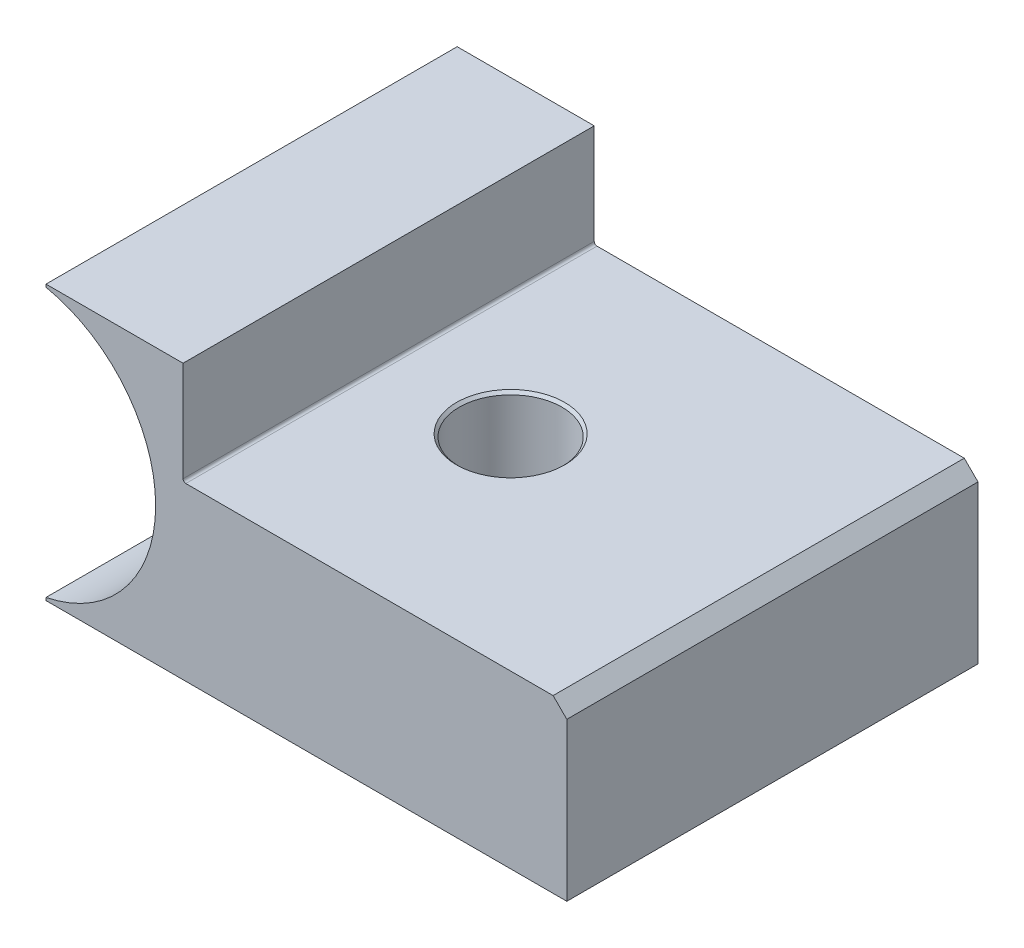
SolidWorks part; units mm, degrees
material "AISI Type A2 Tool Steel Custom"
ref_plane "Front Plane" through (0, 0, 0) normal (0, 0, 1) x (1, 0, 0)
ref_plane "Top Plane" through (0, 0, 0) normal (0, 1, 0) x (1, 0, 0)
ref_plane "Right Plane" through (0, 0, 0) normal (1, 0, 0) x (0, 0, -1)
sketch "Sketch1" plane through (0, 0, 0) normal (0, 0, 1) x (1, 0, 0)
  line L1 (2.54, 0) -> (50.8, 0)
  line L3 (2.54, 25.4) -> (15.24, 25.4)
  line L4 (50.8, 0) -> (50.8, 15.875)
  line L5 (2.54, 25.4) -> (2.54, 25.1434)
  line L6 (15.24, 25.4) -> (15.24, 15.875)
  line L7 (15.24, 15.875) -> (50.8, 15.875)
  line L8 (2.54, 0.2566) -> (2.54, 0)
  arc A1 (2.54, 0.2566) -> (2.54, 25.1434) centre (0, 12.7) ccw
  dimension "D2" = 25.4
  dimension "D1" = 12.7
  dimension "D3" = 9.525
  dimension "D4" = 2.54
  dimension "D5" = 35.56
  dimension "D6" = 15.875
  dimension "D7" = 0.2566
extrude "Boss-Extrude1" add sketch "Sketch1" along normal blind 38.1
sketch "Sketch2" plane through (0, 15.875, 0) normal (0, 1, 0) x (1, 0, 0)
  line L0 (0, -38.1) -> (0, 0) construction
  point P0 (26.543, -19.05)
  point P5 (0, -19.05)
  dimension "D1" = 26.543
hole_wizard "3/8 (0.375) Diameter Hole1" positions "Sketch2" profile "Sketch4" hole size "3/8" standard "ANSI Inch" end condition through all
sketch "Sketch4" plane through (26.543, 15.875, 19.05) normal (1, 0, 0) x (0, 0, 1)
  line L0 (0, 0) -> (0, 15.875)
  line L1 (0, 15.875) -> (4.7625, 15.875)
  line L2 (4.7625, 15.875) -> (4.7625, 0)
  line L5 (4.7625, 0) -> (0, 0)
  line L11 (0, -6.35) -> (0, 107.95) construction
  dimension "Thru Hole Dia." = 9.525
  dimension "Thru Hole Depth" = 15.875
chamfer "Chamfer1" distance 1.27 angle 45 1 edges at (50.8, 15.875, 19.05)
chamfer "Chamfer2" distance 0.254 angle 45 1 edges at (26.543, 15.875, 23.8125)
fillet "Fillet1" radius 0.254 1 edges at (15.24, 15.875, 19.05)
